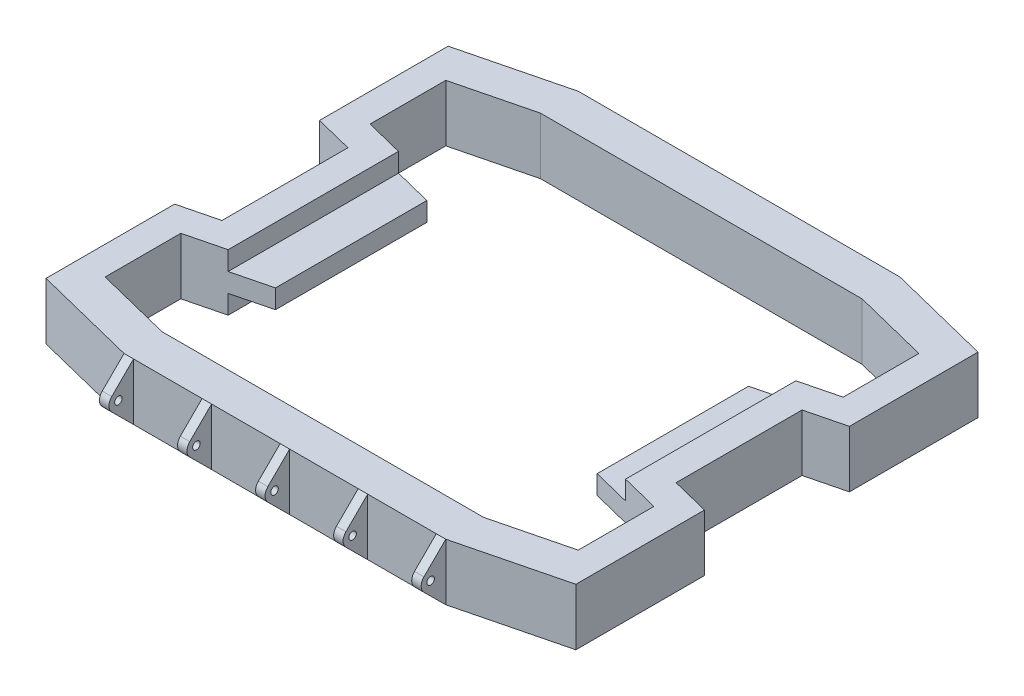
SolidWorks part; units mm, degrees
ref_plane "Front Plane" through (0, 0, 0) normal (0, 0, 1) x (1, 0, 0)
ref_plane "Top Plane" through (0, 0, 0) normal (0, 1, 0) x (1, 0, 0)
ref_plane "Right Plane" through (0, 0, 0) normal (1, 0, 0) x (0, 0, -1)
sketch "Sketch1" plane through (0, 0, 0) normal (0, 1, 0) x (1, 0, 0)
  line L0 (-69.85, 175.6262) -> (-44.45, 169.2762)
  line L1 (0, 0) -> (215.9, 0) construction
  line L2 (0, 0) -> (0, 254) construction
  line L3 (0, 254) -> (215.9, 254) construction
  line L4 (215.9, 0) -> (215.9, 254) construction
  line L5 (-69.85, 175.6262) -> (-69.85, 261.9375)
  line L6 (-69.85, 261.9375) -> (0, 279.4)
  line L7 (0, 177.8) -> (0, 76.2)
  line L8 (0, 177.8) -> (-50.8, 190.5)
  line L9 (-50.8, 190.5) -> (-50.8, 241.3)
  line L10 (-50.8, 241.3) -> (0, 254)
  line L11 (-44.45, 169.2762) -> (-44.45, 84.7238)
  line L12 (0, 254) -> (215.9, 254)
  line L13 (0, 279.4) -> (215.9, 279.4)
  line L14 (107.95, 254) -> (107.95, 0) construction
  line L15 (0, 127) -> (215.9, 127) construction
  line L16 (260.35, 169.2762) -> (260.35, 84.7238)
  line L17 (266.7, 241.3) -> (215.9, 254)
  line L18 (215.9, 177.8) -> (266.7, 190.5)
  line L19 (215.9, 177.8) -> (215.9, 76.2)
  line L20 (285.75, 261.9375) -> (215.9, 279.4)
  line L21 (266.7, 190.5) -> (266.7, 241.3)
  line L22 (285.75, 175.6262) -> (285.75, 261.9375)
  line L23 (285.75, 175.6262) -> (260.35, 169.2762)
  line L24 (0, 0) -> (215.9, 0) construction
  line L25 (285.75, 78.3738) -> (260.35, 84.7238)
  line L26 (285.75, 78.3738) -> (285.75, -7.9375)
  line L27 (266.7, 63.5) -> (266.7, 12.7)
  line L28 (285.75, -7.9375) -> (215.9, -25.4)
  line L29 (215.9, 76.2) -> (266.7, 63.5)
  line L30 (266.7, 12.7) -> (215.9, 0)
  line L31 (0, -25.4) -> (215.9, -25.4)
  line L32 (0, 0) -> (215.9, 0)
  line L33 (-50.8, 12.7) -> (0, 0)
  line L34 (-50.8, 63.5) -> (-50.8, 12.7)
  line L35 (0, 76.2) -> (-50.8, 63.5)
  line L36 (-69.85, -7.9375) -> (0, -25.4)
  line L37 (-69.85, 78.3738) -> (-69.85, -7.9375)
  line L38 (-69.85, 78.3738) -> (-44.45, 84.7238)
  line L39 (-25.4, 69.85) -> (-25.4, 184.15)
  line L40 (241.3, 69.85) -> (241.3, 184.15)
  point P5 (-50.8, 215.9)
  point P9 (0, 127)
  point P13 (107.95, 254)
  point P22 (107.95, 279.4)
  point P28 (215.9, 127)
  point P30 (266.7, 215.9)
  point P38 (260.35, 127)
  point P40 (-44.45, 127)
  point P45 (266.7, 38.1)
  point P46 (107.95, -25.4)
  point P47 (107.95, 0)
  point P48 (-50.8, 38.1)
  dimension "D1" = 254
  dimension "D2" = 215.9
  dimension "D3" = 50.8
  dimension "D4" = 50.8
  dimension "D5" = 38.1
  dimension "D6" = 19.05
  dimension "D7" = 19.05
  dimension "D8" = 25.4
  dimension "D9" = 19.05
  dimension "D10" = 25.4
extrude "Boss-Extrude1" add sketch "Sketch1" along normal blind 38.1 contours L38 L37 L36 L31 L28 L26 L25 L16 L23 L22 L20 L13 L6 L5 L0 L11 L40 L29 L27 L30 L32 L33 L34 L35 L39 L8 L9 L10 L12 L17 L21 L18 region at (-65.1665, 0, -218.7819)
sketch "Sketch2" plane through (0, 0, 0) normal (1, 0, 0) x (0, 0, -1)
  line L0 (-40.0362, 23.554) -> (-25.4, 38.1)
  line L1 (-40.0362, 14.546) -> (-25.4, 0)
  line L2 (-25.4, 0) -> (-25.4, 38.1)
  circle A0 centre (-35.56, 19.05) radius 2.54
  arc A1 (-40.0362, 23.554) -> (-40.0362, 14.546) centre (-35.56, 19.05) ccw
  point P10 (-25.4, 19.05)
  dimension "D1" = 3.81
  dimension "D2" = 5.08
  dimension "D3" = 10.16
extrude "Boss-Extrude2" add sketch "Sketch2" along normal blind 6.35
pattern_linear "LPattern1" count 5 spacing 52.3875 along (1, 0, 0) of "Boss-Extrude2"
extrude "Boss-Extrude3" add sketch "Sketch1<3>" along normal offset from surface (25.4 mm away) 12.7 contours L39 L35 L7 L8 | L29 L40 L18 L19 region at (-12.949, 0, -127) region at (228.849, 0, -127) up to face at (107.95, 38.1, -127)
sketch "Sketch1<3>" plane through (0, 0, 0) normal (0, 1, 0) x (1, 0, 0) same geometry as "Sketch1"
extrude "Cut-Extrude1" cut sketch "Sketch1<4>" along normal blind 12.7 contours L39 L35 L7 L8 | L29 L40 L18 L19 region at (-12.949, 0, -127) region at (228.849, 0, -127)
sketch "Sketch1<4>" plane through (0, 0, 0) normal (0, 1, 0) x (1, 0, 0) same geometry as "Sketch1"
